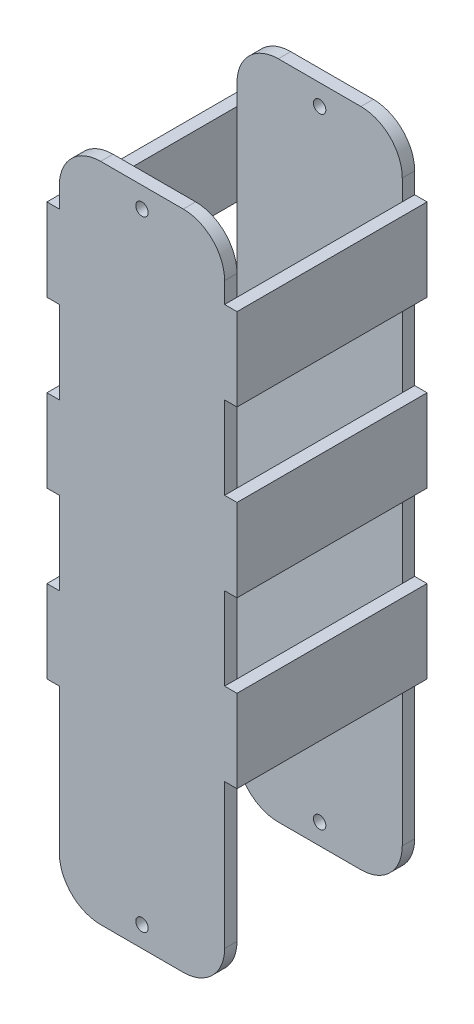
SolidWorks part; units mm, degrees
material "ENPH 253 Hardboard"
ref_plane "Front Plane" through (0, 0, 0) normal (0, 0, 1) x (1, 0, 0)
ref_plane "Top Plane" through (0, 0, 0) normal (0, 1, 0) x (1, 0, 0)
ref_plane "Right Plane" through (0, 0, 0) normal (1, 0, 0) x (0, 0, -1)
sketch "Sketch1" plane through (0, 0, 0) normal (0, 0, 1) x (1, 0, 0)
  line L1 (-10, 80) -> (10, 80)
  line L2 (-20, 70) -> (-20, -70)
  line L3 (-10, -80) -> (10, -80)
  line L4 (20, 70) -> (20, -70)
  line L5 (-20, 80) -> (20, -80) construction
  line L6 (-20, -80) -> (20, 80) construction
  arc A0 (10, -80) -> (20, -70) centre (10, -70) ccw
  arc A1 (-20, -70) -> (-10, -80) centre (-10, -70) ccw
  arc A2 (10, 80) -> (20, 70) centre (10, 70) cw
  arc A3 (-20, 70) -> (-10, 80) centre (-10, 70) cw
  point P0 (0, 0)
  dimension "D3" = 10
  dimension "D1" = 40
  dimension "D2" = 160
extrude "Boss-Extrude1" add sketch "Sketch1" along normal blind 3 from offset 40 contours L4 A0 L3 A1 L2 A3 L1 A2
extrude "Boss-Extrude2" add sketch "Sketch1<3>" against normal blind 3 separate body
sketch "Sketch1<3>" plane through (0, 0, 0) normal (0, 0, 1) x (1, 0, 0) same geometry as "Sketch1"
sketch "Sketch2" plane through (0, 0, 0) normal (0, 0, 1) x (1, 0, 0)
  line L0 (55, 0) -> (-55, 0) construction
  line L1 (-10, 80) -> (10, 80) construction
  circle A0 centre (0, 75) radius 1.5
  circle A1 centre (0, -75) radius 1.5
  dimension "D2" = 3
  dimension "D1" = 5
extrude "Cut-Extrude1" cut sketch "Sketch2" against normal through all both and the other way through all
sketch "Sketch3" plane through (-20, 0, 0) normal (-1, 0, 0) x (0, 0, 1)
  line L0 (-3, 70) -> (-3, -70) construction
  line L1 (-3, 65) -> (43, 65)
  line L2 (-3, 65) -> (-3, 45)
  line L3 (-3, 45) -> (43, 45)
  line L4 (43, 65) -> (43, 45)
  line L5 (43, 70) -> (43, -70) construction
  line L6 (43, 80) -> (40, 80) construction
  line L7 (-3, 25) -> (-3, 5)
  line L8 (-3, 25) -> (43, 25)
  line L9 (43, 25) -> (43, 5)
  line L10 (-3, 5) -> (43, 5)
  line L11 (-3, -15) -> (-3, -35)
  line L12 (-3, -15) -> (43, -15)
  line L13 (43, -15) -> (43, -35)
  line L14 (-3, -35) -> (43, -35)
  dimension "D1" = 20
  dimension "D2" = 15
  dimension "D3" = 3
extrude "Boss-Extrude4" add sketch "Sketch3" along normal blind 3
mirror "Mirror1" about plane through (0, 0, 0) normal (1, 0, 0) of "Boss-Extrude4"
